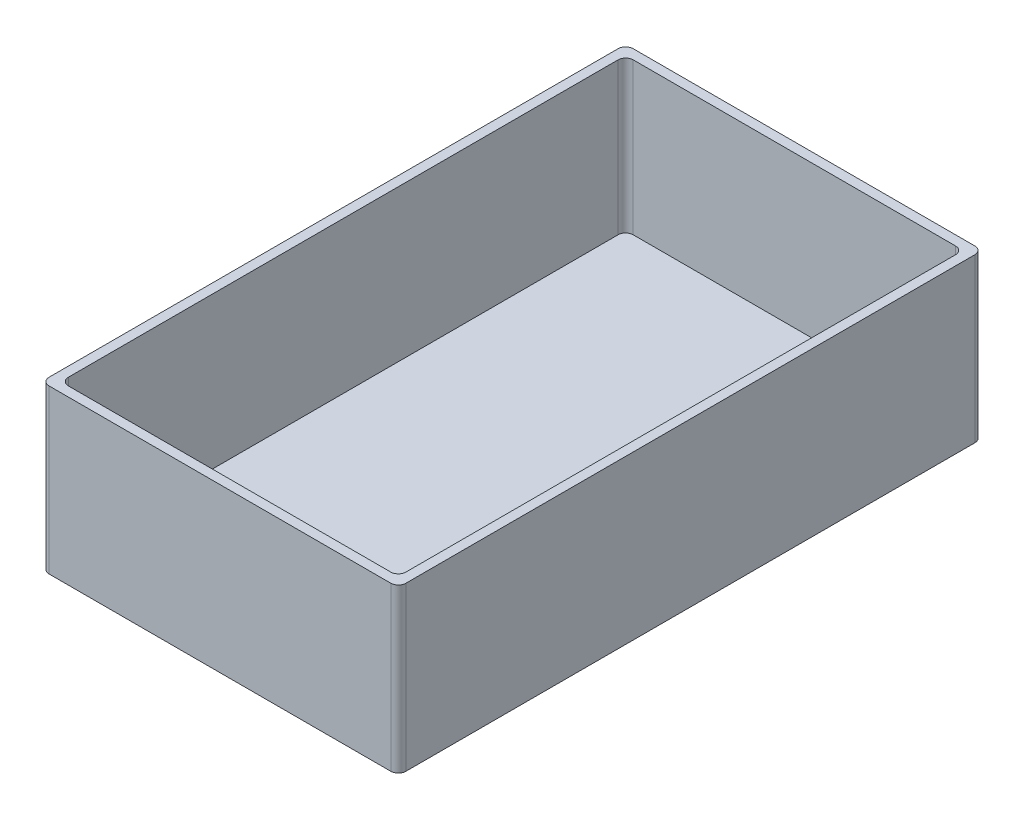
SolidWorks part; units mm, degrees
ref_plane "Front Plane" through (0, 0, 0) normal (0, 0, 1) x (1, 0, 0)
ref_plane "Top Plane" through (0, 0, 0) normal (0, 1, 0) x (1, 0, 0)
ref_plane "Right Plane" through (0, 0, 0) normal (1, 0, 0) x (0, 0, -1)
sketch "Sketch1" plane through (0, 0, 0) normal (0, 1, 0) x (1, 0, 0)
  line L5 (0, 0) -> (47.0912, 0)
  line L6 (0, 0) -> (0, -77.0912)
  line L7 (0, -77.0912) -> (47.0912, -77.0912)
  line L8 (47.0912, 0) -> (47.0912, -77.0912)
extrude "Boss-Extrude1" add sketch "Sketch1" along normal blind 1.5
sketch "Sketch2" plane through (0, 1.5, 0) normal (0, 1, 0) x (1, 0, 0)
  line L3 (1.2728, -1.2728) -> (45.8184, -1.2728)
  line L4 (1.2728, -1.2728) -> (1.2728, -75.8184)
  line L5 (1.2728, -75.8184) -> (45.8184, -75.8184)
  line L6 (45.8184, -1.2728) -> (45.8184, -75.8184)
  line L7 (0, 0) -> (47.0912, 0)
  line L8 (0, 0) -> (0, -77.0912)
  line L9 (0, -77.0912) -> (47.0912, -77.0912)
  line L10 (47.0912, 0) -> (47.0912, -77.0912)
extrude "Boss-Extrude2" add sketch "Sketch2" along normal blind 20
fillet "Fillet4" radius 1 8 edges at (45.8184, 11.5, 1.2728) (1.2728, 11.5, 1.2728) (45.8184, 11.5, 75.8184) (1.2728, 11.5, 75.8184) (47.0912, 10.75, 0) (0, 10.75, 0) (47.0912, 10.75, 77.0912) (0, 10.75, 77.0912)
sketch "Sketch3" plane through (0, 1.5, 0) normal (0, 1, 0) x (1, 0, 0)
  line L1 (2.2728, -2.2728) -> (44.8184, -2.2728)
  line L2 (2.2728, -2.2728) -> (2.2728, -74.8184)
  line L3 (2.2728, -74.8184) -> (44.8184, -74.8184)
  line L4 (44.8184, -2.2728) -> (44.8184, -74.8184)
sketch "Sketch5" plane through (0, 0, 0) normal (0, 0, -1) x (-1, 0, 0)
  line L0 (-44.8184, 1.5) -> (-44.2034, 1.5)
  line L1 (-2.2728, 1.5) -> (-44.8184, 1.5) construction
  line L4 (-44.2034, 1.5) -> (-35.8034, 1.5)
  line L5 (-44.2034, 1.5) -> (-44.2034, 4.1)
  line L6 (-44.2034, 4.1) -> (-35.8034, 4.1)
  line L7 (-35.8034, 1.5) -> (-35.8034, 4.1)
extrude "Cut-Extrude1" cut sketch "Sketch5" against normal blind 10 contours L5 L6 L7 L4
fillet "Fillet8" radius 1 4 edges at (35.8034, 1.5, 0.6364) (35.8034, 4.1, 0.6364) (44.2034, 1.5, 0.6364) (44.2034, 4.1, 0.6364)
sketch "Sketch7" plane through (0, 0, 0) normal (-1, 0, 0) x (0, 0, 1)
  text T0 "Band" font "Dutch801 XBd BT" height in points 22
  text T1 "3" font "Dutch801 XBd BT" height in points 9
extrude "Cut-Extrude2" cut sketch "Sketch7" against normal blind 1
